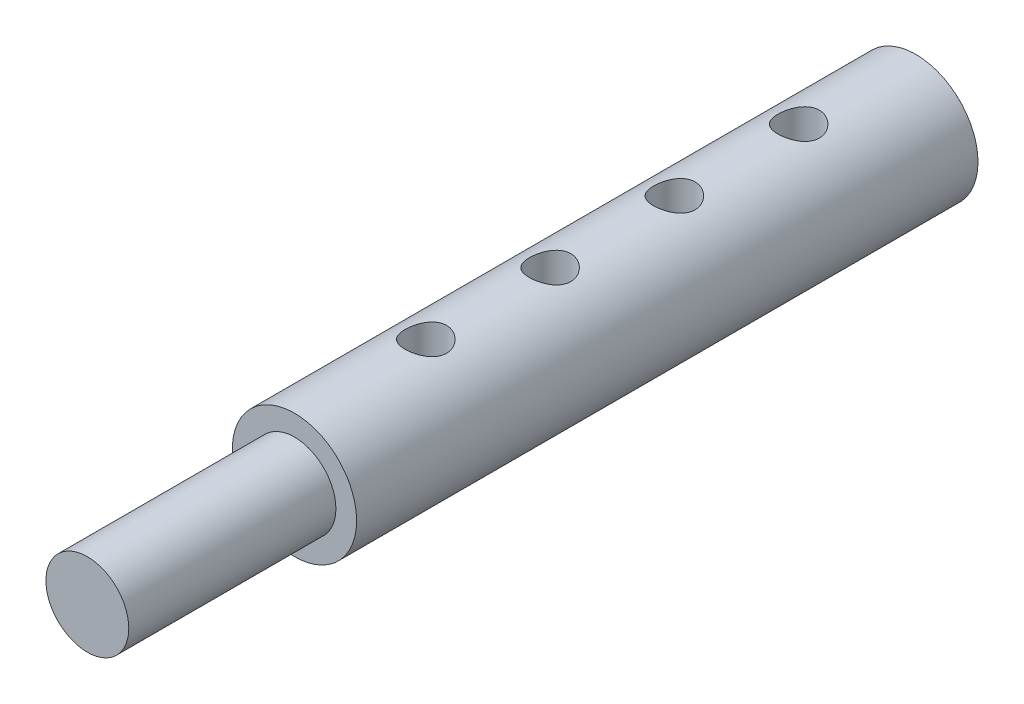
SolidWorks part; units mm, degrees
ref_plane "Płaszczyzna przednia" through (0, 0, 0) normal (0, 0, 1) x (1, 0, 0)
ref_plane "Płaszczyzna górna" through (0, 0, 0) normal (0, 1, 0) x (1, 0, 0)
ref_plane "Płaszczyzna prawa" through (0, 0, 0) normal (1, 0, 0) x (0, 0, -1)
sketch "Szkic1" plane through (0, 0, 0) normal (0, 0, 1) x (1, 0, 0)
  circle A0 centre (0, 0) radius 15
extrude "Dodanie-wyciągnięcie1" add sketch "Szkic1" along normal blind 150
sketch "Szkic2" plane through (0, 0, 150) normal (0, 0, 1) x (1, 0, 0)
  circle A0 centre (0, 0) radius 10
extrude "Dodanie-wyciągnięcie2" add sketch "Szkic2" along normal blind 50
sketch "Szkic3" plane through (0, 0, 0) normal (0, 1, 0) x (1, 0, 0)
  circle A0 centre (0, -28.3036) radius 5
  circle A1 centre (0, -58.3036) radius 5
  circle A2 centre (0, -88.3036) radius 5
  circle A3 centre (0, -118.3036) radius 5
  circle A5 centre (0, -148.3036) radius 5 [skipped]
  dimension "D1" = 5
extrude "Wytnij-wyciągnięcie1" cut sketch "Szkic3" against normal blind 70 and the other way blind 70
